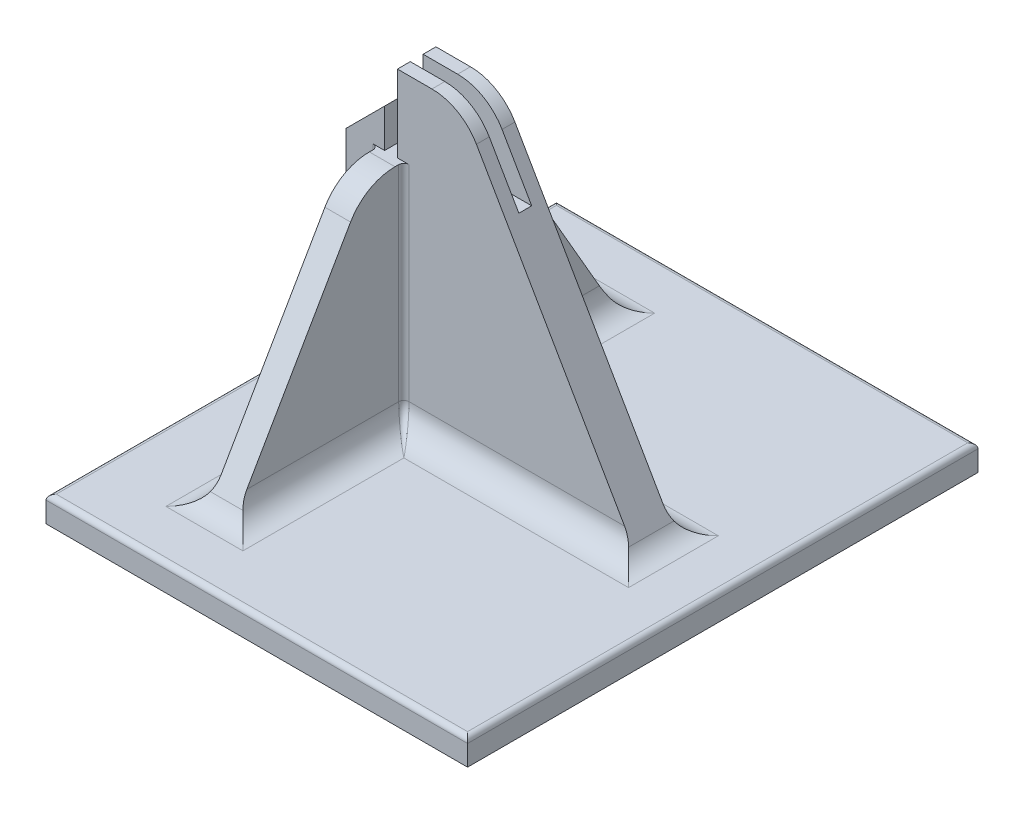
SolidWorks part; units mm, degrees
material "7075-T6, Plate (SS)"
ref_plane "Front Plane" through (0, 0, 0) normal (0, 0, 1) x (1, 0, 0)
ref_plane "Top Plane" through (0, 0, 0) normal (0, 1, 0) x (1, 0, 0)
ref_plane "Right Plane" through (0, 0, 0) normal (1, 0, 0) x (0, 0, -1)
sketch "Sketch1" plane through (0, 0, 0) normal (0, 0, 1) x (1, 0, 0)
  line L8 (0, 0) -> (0, 30)
  line L9 (0, 30) -> (25, 30)
  line L10 (25, 30) -> (94.282, -90)
  line L11 (94.282, -90) -> (-20, -90)
  line L12 (-20, -90) -> (-20, 0)
  line L13 (-20, 0) -> (-5, 15)
  line L14 (-5, 15) -> (-5, 0)
  line L15 (-5, 0) -> (0, 0)
  dimension "D1" = 30
  dimension "D2" = 90
  dimension "D3" = 25
  dimension "D4" = 15
  dimension "D5" = 30
  dimension "D6" = 45
  dimension "D7" = 5
extrude "Boss-Extrude1" add sketch "Sketch1" along normal mid plane 15
sketch "Sketch2" plane through (0, 0, 0) normal (1, 0, 0) x (0, 0, -1)
  line L0 (-7.5, -90) -> (-74.4615, -90)
  line L1 (-74.4615, -90) -> (-22.5, 0)
  line L2 (-22.5, 0) -> (-7.5, 0)
  line L3 (-7.5, 0) -> (-7.5, -90)
  line L4 (7.5, -90) -> (7.5, 30)
  line L5 (7.5, 30) -> (-7.5, 30)
  line L6 (-7.5, 30) -> (-7.5, -90)
  line L7 (-7.5, -90) -> (7.5, -90)
  line L8 (7.5, -90) -> (7.5, 30) construction
  line L9 (7.5, 30) -> (-7.5, 30) construction
  line L10 (-7.5, 30) -> (-7.5, -90) construction
  line L11 (-7.5, -90) -> (7.5, -90) construction
  line L12 (0, 0) -> (0, -50000) construction
  line L13 (7.5, 0) -> (7.5, -90)
  line L14 (22.5, 0) -> (7.5, 0)
  line L15 (74.4615, -90) -> (22.5, 0)
  line L16 (7.5, -90) -> (74.4615, -90)
  dimension "D2" = 30
  dimension "D3" = 15
  dimension "D1" = 0
extrude "Boss-Extrude2" add sketch "Sketch2" against normal blind 7.5 and the other way blind 2.5
sketch "Sketch3" plane through (0, -90, 0) normal (0, -1, 0) x (1, 0, 0)
  line L8 (-45, 99.4615) -> (-45, -99.4615)
  line L9 (-45, -99.4615) -> (119.282, -99.4615)
  line L10 (119.282, -99.4615) -> (119.282, 99.4615)
  line L11 (119.282, 99.4615) -> (-45, 99.4615)
  line L20 (-20, -7.5) -> (-7.5, -7.5)
  line L21 (-7.5, -7.5) -> (-7.5, -74.4615)
  line L22 (-7.5, -74.4615) -> (2.5, -74.4615)
  line L23 (2.5, -74.4615) -> (2.5, -7.5)
  line L24 (2.5, -7.5) -> (94.282, -7.5)
  line L25 (94.282, -7.5) -> (94.282, 7.5)
  line L26 (94.282, 7.5) -> (2.5, 7.5)
  line L27 (2.5, 7.5) -> (2.5, 74.4615)
  line L28 (2.5, 74.4615) -> (-7.5, 74.4615)
  line L29 (-7.5, 74.4615) -> (-7.5, 7.5)
  line L30 (-7.5, 7.5) -> (-20, 7.5)
  line L31 (-20, 7.5) -> (-20, -7.5)
  line L32 (-20, -7.5) -> (-7.5, -7.5) construction
  line L33 (-7.5, -7.5) -> (-7.5, -74.4615) construction
  line L34 (-7.5, -74.4615) -> (2.5, -74.4615) construction
  line L35 (2.5, -74.4615) -> (2.5, -7.5) construction
  line L36 (2.5, -7.5) -> (94.282, -7.5) construction
  line L37 (94.282, -7.5) -> (94.282, 7.5) construction
  line L38 (94.282, 7.5) -> (2.5, 7.5) construction
  line L39 (2.5, 7.5) -> (2.5, 74.4615) construction
  line L40 (2.5, 74.4615) -> (-7.5, 74.4615) construction
  line L41 (-7.5, 74.4615) -> (-7.5, 7.5) construction
  line L42 (-7.5, 7.5) -> (-20, 7.5) construction
  line L43 (-20, 7.5) -> (-20, -7.5) construction
  dimension "D1" = 25
  dimension "D2" = 25
  dimension "D3" = 25
  dimension "D4" = 25
  dimension "D5" = 0
extrude "Boss-Extrude3" add sketch "Sketch3" along normal blind 10
sketch "Sketch4" plane through (0, 0, 0) normal (1, 0, 0) x (0, 0, -1)
  line L0 (-2.5, 30) -> (2.5, 30)
  line L1 (2.5, 30) -> (2.5, 0)
  line L2 (2.5, 0) -> (-2.5, 0)
  line L3 (-2.5, 0) -> (-2.5, 30)
  line L4 (7.5, 0) -> (7.5, 30)
  line L5 (-7.5, 0) -> (7.5, 0)
  line L6 (-7.5, 30) -> (-7.5, 0)
  line L7 (7.5, 30) -> (-7.5, 30)
  line L8 (7.5, 0) -> (7.5, 30) construction
  line L9 (-7.5, 0) -> (7.5, 0) construction
  line L10 (-7.5, 30) -> (-7.5, 0) construction
  line L11 (7.5, 30) -> (-7.5, 30) construction
  line L12 (-7.5, 30) -> (7.5, 30) construction
  dimension "D2" = 5
  dimension "D3" = 2.5
  dimension "D1" = 0
extrude "Cut-Extrude1" cut sketch "Sketch4" against normal through all both and the other way through all
fillet "Fillet1" radius 10 12 edges at (-13.75, -90, 7.5) (-7.5, -90, 40.9808) (-20, -90, 0) (-13.75, -90, -7.5) (-7.5, -90, -40.9808) (-2.5, -90, -74.4615) (2.5, -90, -40.9808) (48.391, -90, -7.5) (94.282, -90, 0) (-2.5, -90, 74.4615) (2.5, -90, 40.9808) (48.391, -90, 7.5)
fillet "Fillet2" radius 20 2 edges at (25, 30, -5) (25, 30, 5)
fillet "Fillet4" radius 20 2 edges at (-2.5, 0, -22.5) (-2.5, 0, 22.5)
fillet "Fillet5" radius 2 4 edges at (-45, -90, 0) (37.141, -90, -99.4615) (119.282, -90, 0) (37.141, -90, 99.4615)
fillet "Fillet6" radius 2 8 edges at (5.4289, -87.0711, -10.4289) (-10.4289, -87.0711, -10.4289) (-10.4289, -87.0711, 10.4289) (5.4289, -87.0711, 10.4289) (2.5, -40, -7.5) (-7.5, -40, -7.5) (-7.5, -40, 7.5) (2.5, -40, 7.5)
